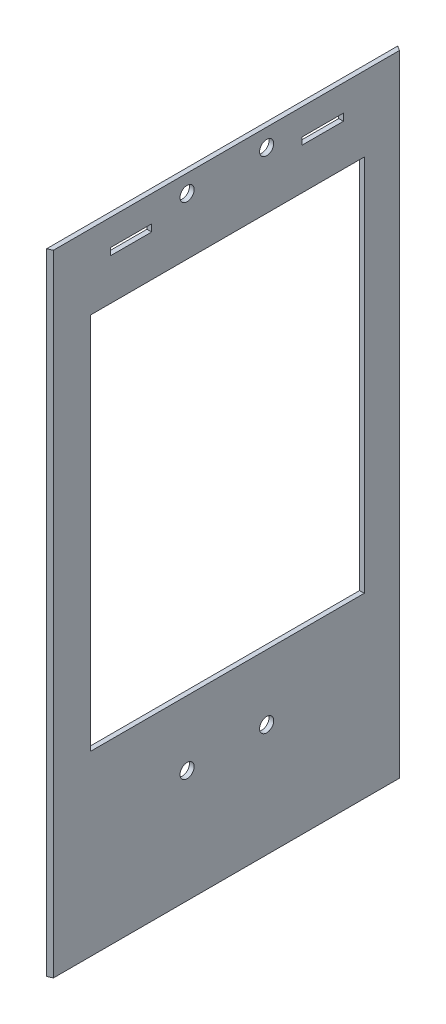
SolidWorks part; units mm, degrees
ref_plane "Спереди" through (0, 0, 0) normal (0, 0, 1) x (1, 0, 0)
ref_plane "Сверху" through (0, 0, 0) normal (0, 1, 0) x (1, 0, 0)
ref_plane "Справа" through (0, 0, 0) normal (1, 0, 0) x (0, 0, -1)
sketch "Эскиз1" plane through (0, 0, 0) normal (0, 1, 0) x (1, 0, 0)
  line L0 (4.0186, 1.7475) -> (79.181, -66.868) construction
  line L1 (0, 0) -> (4, 1.7645)
  line L2 (0, 0) -> (0, 297.3876)
  line L3 (0, 297.3876) -> (4, 294.8273)
  line L4 (4, 1.7645) -> (4, 294.8273)
  dimension "D1" = 4
extrude "Вытянуть1" add sketch "Эскиз1" along normal up to surface (533.7137 mm away)
sketch "Эскиз2" plane through (0, 0, 0) normal (-1, 0, 0) x (0, 0, 1)
  line L0 (-272.3275, 260.902) -> (-272.3275, -22.3628)
  line L1 (-272.3275, 260.902) -> (-25.1909, 260.902)
  line L3 (-272.3275, -22.3628) -> (-25.1909, -22.3628)
  line L4 (-25.1909, 260.902) -> (-25.1909, -22.3628)
  line L6 (-264.3275, 152.3571) -> (-192.5685, 152.3571) construction
sketch "Sketch1" plane through (0, 0, 0) normal (-1, 0, 0) x (0, 0, 1)
  line L0 (-149.0559, 533.7137) -> (-149.0559, 365.9424) construction
  line L2 (-466.2387, 150.5) -> (190.429, 150.5) construction
  line L3 (-297.6324, 0.5) -> (0.0403, 0.5) construction
  line L4 (-507.1548, 470.5) -> (192.6943, 470.5) construction
  line L5 (-451.9035, 310.5) -> (226.1799, 310.5) construction
  line L7 (-33.0559, 150.5) -> (-265.0559, 150.5)
  line L8 (-33.0559, 150.5) -> (-33.0559, 470.5)
  line L9 (-33.0559, 470.5) -> (-265.0559, 470.5)
  line L10 (-265.0559, 150.5) -> (-265.0559, 470.5)
  line L11 (-33.0559, 150.5) -> (-265.0559, 470.5) construction
  line L12 (-33.0559, 470.5) -> (-265.0559, 150.5) construction
  point P9 (-149.0559, 310.5)
  dimension "D1" = 150
  dimension "D2" = 320
  dimension "D3" = 160
extrude "Cut-Extrude1" cut sketch "Sketch1" against normal through all
sketch "Sketch2" plane through (0, 0, 0) normal (-1, 0, 0) x (0, 0, 1)
  line L0 (-325.7416, 505.5) -> (32.5763, 505.5) construction
  line L1 (-33.0559, 470.5) -> (-265.0559, 470.5) construction
  line L2 (-247.3876, 583.7888) -> (-247.3876, 553.0639) construction
  line L4 (-297.3876, 533.7137) -> (-297.3876, 0) construction
  line L5 (-148.6938, 533.7137) -> (-148.6938, 623.8727) construction
  line L6 (-247.3876, 505.5) -> (-212.3876, 505.5)
  line L7 (-247.3876, 505.5) -> (-247.3876, 511.5)
  line L8 (-247.3876, 511.5) -> (-212.3876, 511.5)
  line L9 (-212.3876, 505.5) -> (-212.3876, 511.5)
  line L11 (-50, 505.5) -> (-50, 511.5)
  line L12 (-50, 505.5) -> (-85, 505.5)
  line L13 (-85, 505.5) -> (-85, 511.5)
  line L14 (-50, 511.5) -> (-85, 511.5)
  dimension "D1" = 35
  dimension "D2" = 50
extrude "Cut-Extrude2" cut sketch "Sketch2" against normal through all
sketch "Sketch3" plane through (0, 0, 0) normal (-1, 0, 0) x (0, 0, 1)
  line L0 (-297.3876, 533.7137) -> (-297.3876, 0) construction
  line L1 (-297.3876, 533.7137) -> (0, 533.7137) construction
  line L2 (0, 533.7137) -> (0, 0) construction
  line L3 (-297.8921, 533.7137) -> (-0.2197, 533.7137) construction
  line L4 (-297.6324, 0.5) -> (0.0403, 0.5) construction
  circle A0 centre (-182.3876, 518.7137) radius 6
  circle A1 centre (-115, 518.7137) radius 6
  circle A2 centre (-182.3876, 95.5) radius 6
  circle A3 centre (-115, 95.5) radius 6
  dimension "D1" = 115
  dimension "D3" = 115
  dimension "D5" = 95
  dimension "D7" = 115
  dimension "D2" = 15
  dimension "D4" = 15
  dimension "D6" = 115
extrude "Cut-Extrude3" cut sketch "Sketch3" against normal through all
